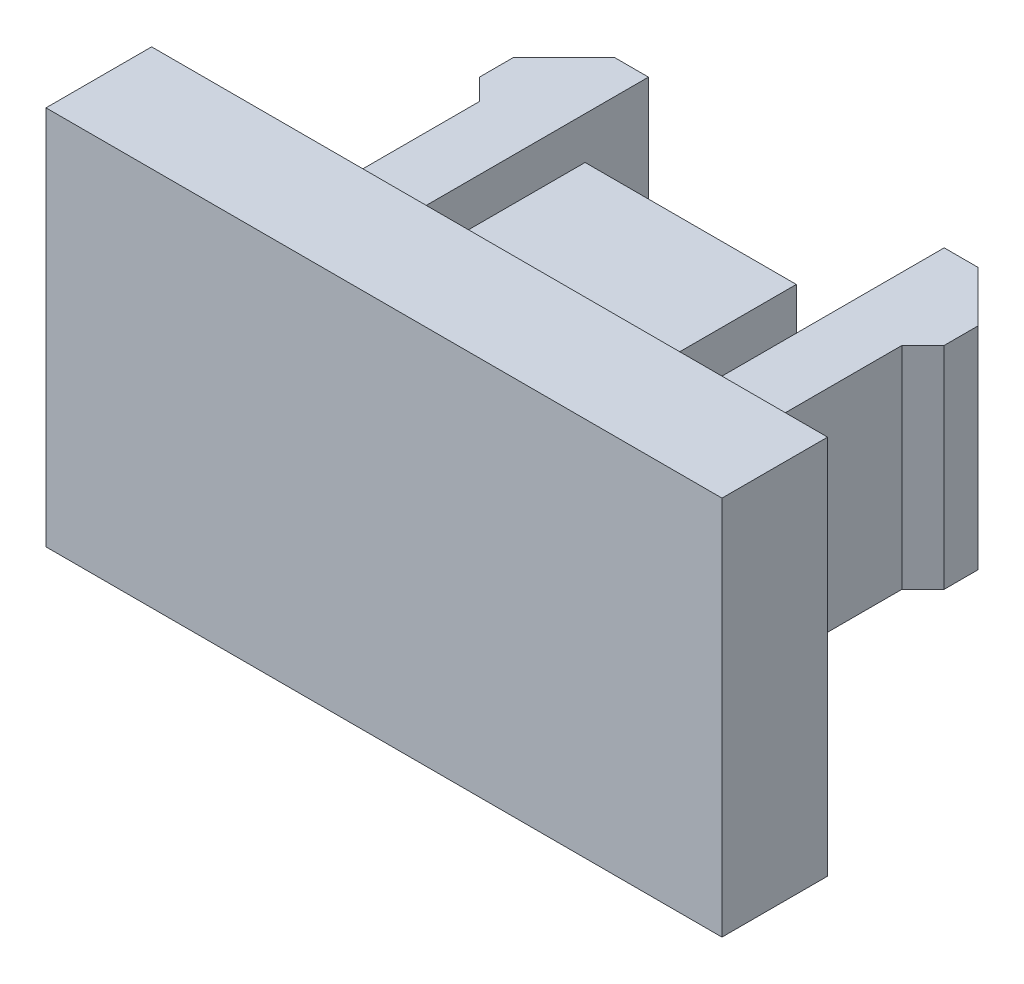
SolidWorks part; units mm, degrees
ref_plane "Front Plane" through (0, 0, 0) normal (0, 0, 1) x (1, 0, 0)
ref_plane "Top Plane" through (0, 0, 0) normal (0, 1, 0) x (1, 0, 0)
ref_plane "Right Plane" through (0, 0, 0) normal (1, 0, 0) x (0, 0, -1)
sketch "Sketch1" plane through (0, 0, 0) normal (0, 1, 0) x (1, 0, 0)
  line L0 (0, 0) -> (0, -3.175)
  line L1 (0, -3.175) -> (20.32, -3.175)
  line L2 (20.32, -3.175) -> (20.32, 0)
  line L3 (20.32, 0) -> (16.51, 0)
  line L4 (3.81, 0) -> (0, 0)
  line L6 (3.81, 0) -> (3.81, 6.0452)
  line L7 (3.81, 6.0452) -> (16.51, 6.0452)
  line L8 (16.51, 0) -> (16.51, 6.0452)
  line L9 (3.81, 6.0452) -> (3.175, 6.6802)
  line L10 (3.175, 6.6802) -> (3.175, 7.6962)
  line L11 (3.175, 7.6962) -> (4.699, 9.2202)
  line L12 (4.699, 9.2202) -> (5.715, 9.2202)
  line L13 (5.715, 9.2202) -> (5.715, 6.0452)
  line L14 (10.16, 6.0452) -> (10.16, 11.1252) construction
  line L15 (16.51, 6.0452) -> (17.145, 6.6802)
  line L16 (17.145, 6.6802) -> (17.145, 7.6962)
  line L17 (17.145, 7.6962) -> (15.621, 9.2202)
  line L18 (15.621, 9.2202) -> (14.605, 9.2202)
  line L19 (14.605, 9.2202) -> (14.605, 6.0452)
  line L20 (3.81, 0) -> (16.51, 0)
  dimension "D1" = 3.175
  dimension "D2" = 20.32
  dimension "D3" = 6.0452
  dimension "D4" = 12.7
  dimension "D5" = 3.175
  dimension "D6" = 1.524
  dimension "D7" = 1.524
  dimension "D8" = 0.635
  dimension "D9" = 0.635
  dimension "D10" = 1.016
  dimension "D11" = 5.08
extrude "Boss-Extrude1" add sketch "Sketch1" along normal mid plane 6.35 contours L3 L8 L7 L6 L4 L0 L1 L2 | L13 L12 L11 L10 L9 L7 | L18 L19 L7 L15 L16 L17 | L20 L4 L0 L1 L2 L3 region at (10.16, 0, 1.5875) region at (10.16, 0, -3.0226) region at (4.6089, 0, -7.487) region at (15.7111, 0, -7.487)
sketch "Sketch2" plane through (0, 3.175, 0) normal (0, 1, 0) x (1, 0, 0)
  line L0 (3.81, 0) -> (0, 0) construction
  line L1 (5.715, 6.0452) -> (6.985, 6.0452)
  line L2 (5.715, 6.0452) -> (5.715, 0)
  line L3 (5.715, 0) -> (6.985, 0)
  line L4 (6.985, 6.0452) -> (6.985, 0)
  line L5 (10.16, 6.0452) -> (10.16, -3.175) construction
  line L6 (5.715, 6.0452) -> (14.605, 6.0452) construction
  line L7 (0, -3.175) -> (20.32, -3.175) construction
  line L8 (14.605, 0) -> (13.335, 0)
  line L9 (13.335, 6.0452) -> (13.335, 0)
  line L10 (14.605, 6.0452) -> (13.335, 6.0452)
  line L11 (14.605, 6.0452) -> (14.605, 0)
  dimension "D1" = 1.27
extrude "Cut-Extrude1" cut sketch "Sketch2" against normal blind 6.35
extrude "Boss-Extrude2" add sketch "Sketch1<3>" along normal mid plane 11.43 contours L20 L4 L0 L1 L2 L3 region at (10.16, 0, 1.5875)
sketch "Sketch1<3>" plane through (0, 0, 0) normal (0, 1, 0) x (1, 0, 0) same geometry as "Sketch1"
